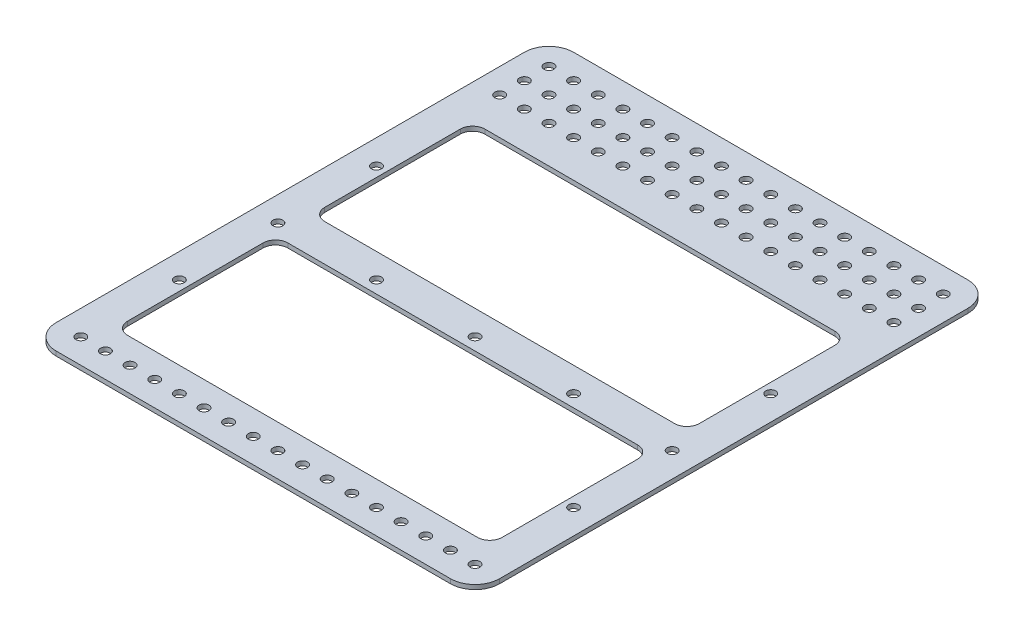
SolidWorks part; units mm, degrees
ref_plane "Front Plane" through (0, 0, 0) normal (0, 0, 1) x (1, 0, 0)
ref_plane "Top Plane" through (0, 0, 0) normal (0, 1, 0) x (1, 0, 0)
ref_plane "Right Plane" through (0, 0, 0) normal (1, 0, 0) x (0, 0, -1)
sketch "Sketch3" plane through (0, 0, 0) normal (0, 1, 0) x (1, 0, 0)
  line B0 (0, 0) -> (228.6, 0)
  line B1 (0, 0) -> (0, 266.7)
  line B2 (0, 266.7) -> (228.6, 266.7)
  line B3 (228.6, 0) -> (228.6, 266.7)
  line B4 (17.78, 107.95) -> (17.78, 25.4)
  line B5 (17.78, 107.95) -> (210.82, 107.95)
  line B6 (210.82, 107.95) -> (210.82, 25.4)
  line B7 (17.78, 127) -> (210.82, 127)
  line B8 (17.78, 127) -> (17.78, 209.55)
  line B9 (17.78, 209.55) -> (210.82, 209.55)
  line B10 (210.82, 127) -> (210.82, 209.55)
  circle B11 centre (12.7, 254) radius 2.54
  circle B12 centre (25.4, 254) radius 2.54
  circle B13 centre (38.1, 254) radius 2.54
  circle B14 centre (50.8, 254) radius 2.54
  circle B15 centre (63.5, 254) radius 2.54
  circle B16 centre (76.2, 254) radius 2.54
  circle B17 centre (88.9, 254) radius 2.54
  circle B18 centre (101.6, 254) radius 2.54
  circle B19 centre (114.3, 254) radius 2.54
  circle B20 centre (127, 254) radius 2.54
  circle B21 centre (139.7, 254) radius 2.54
  circle B22 centre (152.4, 254) radius 2.54
  circle B23 centre (165.1, 254) radius 2.54
  circle B24 centre (177.8, 254) radius 2.54
  circle B25 centre (190.5, 254) radius 2.54
  circle B26 centre (203.2, 254) radius 2.54
  circle B27 centre (215.9, 254) radius 2.54
  circle B28 centre (25.4, 241.3) radius 2.54
  circle B29 centre (38.1, 241.3) radius 2.54
  circle B30 centre (50.8, 241.3) radius 2.54
  circle B31 centre (63.5, 241.3) radius 2.54
  circle B32 centre (76.2, 241.3) radius 2.54
  circle B33 centre (88.9, 241.3) radius 2.54
  circle B34 centre (101.6, 241.3) radius 2.54
  circle B35 centre (114.3, 241.3) radius 2.54
  circle B36 centre (127, 241.3) radius 2.54
  circle B37 centre (139.7, 241.3) radius 2.54
  circle B38 centre (152.4, 241.3) radius 2.54
  circle B39 centre (165.1, 241.3) radius 2.54
  circle B40 centre (177.8, 241.3) radius 2.54
  circle B41 centre (190.5, 241.3) radius 2.54
  circle B42 centre (203.2, 241.3) radius 2.54
  circle B43 centre (215.9, 241.3) radius 2.54
  circle B44 centre (25.4, 228.6) radius 2.54
  circle B45 centre (38.1, 228.6) radius 2.54
  circle B46 centre (50.8, 228.6) radius 2.54
  circle B47 centre (63.5, 228.6) radius 2.54
  circle B48 centre (76.2, 228.6) radius 2.54
  circle B49 centre (88.9, 228.6) radius 2.54
  circle B50 centre (101.6, 228.6) radius 2.54
  circle B51 centre (114.3, 228.6) radius 2.54
  circle B52 centre (127, 228.6) radius 2.54
  circle B53 centre (139.7, 228.6) radius 2.54
  circle B54 centre (152.4, 228.6) radius 2.54
  circle B55 centre (165.1, 228.6) radius 2.54
  circle B56 centre (177.8, 228.6) radius 2.54
  circle B57 centre (190.5, 228.6) radius 2.54
  circle B58 centre (203.2, 228.6) radius 2.54
  circle B59 centre (215.9, 228.6) radius 2.54
  circle B60 centre (12.7, 241.3) radius 2.54
  circle B61 centre (12.7, 228.6) radius 2.54
  circle B62 centre (12.7, 12.7) radius 2.54
  circle B63 centre (25.4, 12.7) radius 2.54
  circle B64 centre (38.1, 12.7) radius 2.54
  circle B65 centre (50.8, 12.7) radius 2.54
  circle B66 centre (63.5, 12.7) radius 2.54
  circle B67 centre (76.2, 12.7) radius 2.54
  circle B68 centre (88.9, 12.7) radius 2.54
  circle B69 centre (101.6, 12.7) radius 2.54
  circle B70 centre (114.3, 12.7) radius 2.54
  circle B71 centre (127, 12.7) radius 2.54
  circle B72 centre (139.7, 12.7) radius 2.54
  circle B73 centre (152.4, 12.7) radius 2.54
  circle B74 centre (165.1, 12.7) radius 2.54
  circle B75 centre (177.8, 12.7) radius 2.54
  circle B76 centre (190.5, 12.7) radius 2.54
  circle B77 centre (203.2, 12.7) radius 2.54
  circle B78 centre (215.9, 12.7) radius 2.54
  circle B79 centre (12.7, 114.3) radius 2.54
  circle B80 centre (63.5, 114.3) radius 2.54
  circle B81 centre (114.3, 114.3) radius 2.54
  circle B82 centre (165.1, 114.3) radius 2.54
  circle B83 centre (215.9, 114.3) radius 2.54
  circle B84 centre (12.7, 165.1) radius 2.54
  circle B85 centre (215.9, 165.1) radius 2.54
  circle B86 centre (12.7, 63.5) radius 2.54
  circle B87 centre (215.9, 63.5) radius 2.54
  line B88 (17.78, 25.4) -> (210.82, 25.4)
sketch_block_instance "Block-Battery Holder-1"
sketch_block "Block-Battery Holder" parameters "D5"=5.08, "D10"=5.08, "D13"=5.08, "D1"=228.6, "D2"=19.05, "D3"=12.7, "D4"=12.7, "D6"=12.7, "D7"=12.7, "D8"=12.7, "D9"=12.7, "D11"=12.7, "D12"=12.7, "D14"=50.8, "D15"=50.8, "D16"=50.8, "D17"=76.2
extrude "Boss-Extrude3" add sketch "Sketch3" along normal blind 2.286
fillet "Fillet5" radius 12.7 4 edges at (0, 1.143, -266.7) (228.6, 1.143, -266.7) (228.6, 1.143, 0) (0, 1.143, 0)
fillet "Fillet6" radius 6.35 8 edges at (17.78, 1.143, -127) (210.82, 1.143, -127) (210.82, 1.143, -209.55) (17.78, 1.143, -209.55) (17.78, 1.143, -107.95) (17.78, 1.143, -25.4) (210.82, 1.143, -25.4) (210.82, 1.143, -107.95)
sketch "Sketch4" plane through (0, 0, 0) normal (0, -1, 0) x (1, 0, 0)
  line L0 (-1000, 0) -> (49000, 0) construction
  line L1 (0, -1000) -> (0, 49000) construction
  point P4 (0, 0)
sketch "Sketch5" [suppressed] plane through (0, 0, 0) normal (0, -1, 0) x (1, 0, 0)
  line L0 (204.47, -203.2) -> (24.13, -203.2) construction
  line L1 (17.78, -196.85) -> (17.78, -133.35) construction
  line L2 (55.88, -165.1) -> (170.18, -165.1) construction
  line L3 (55.88, -165.1) -> (55.88, -50.8) construction
  circle A0 centre (55.88, -165.1) radius 2.54
  circle A1 centre (170.18, -165.1) radius 2.54
  circle A2 centre (170.18, -50.8) radius 2.54
  circle A3 centre (55.88, -50.8) radius 2.54
  dimension "D1" = 38.1
  dimension "D2" = 38.1
  dimension "D3" = 5.08
  dimension "D6" = 114.3
  dimension "D7" = 114.3
  dimension "D4" = 2
  dimension "D5" = 2
